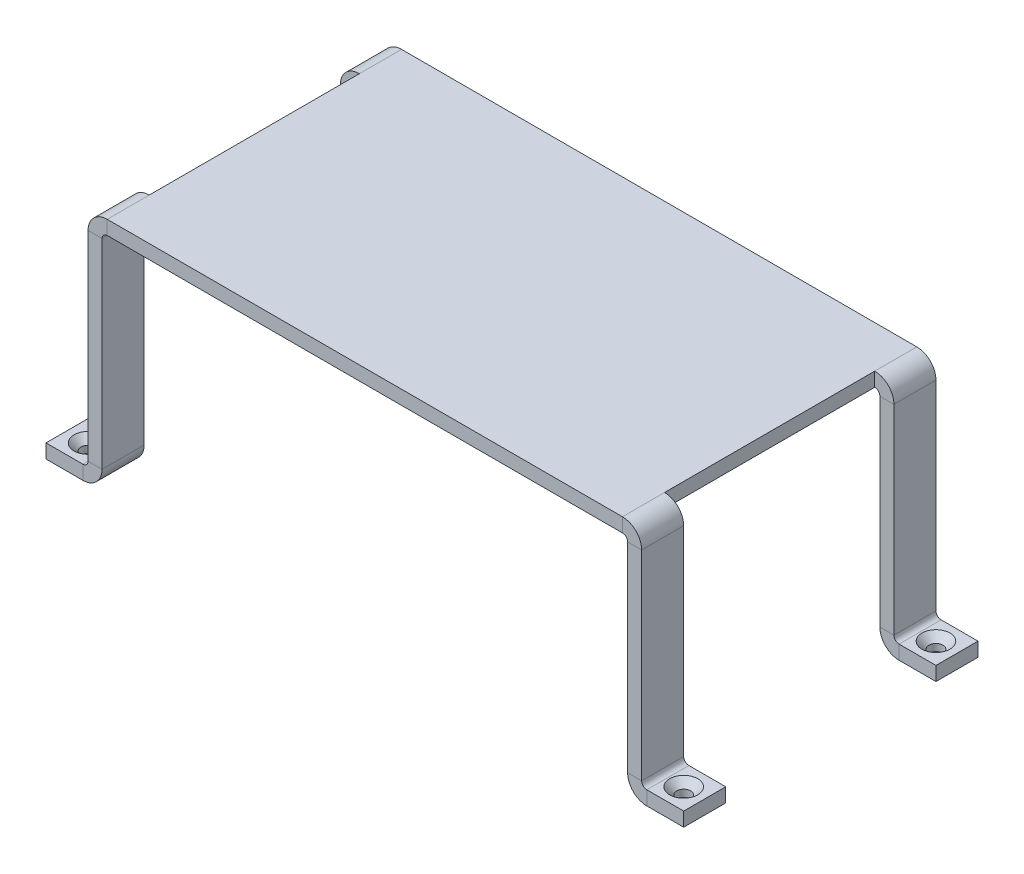
SolidWorks part; units mm, degrees
note: The reader was unsure of these and kept them because the rebuilt part matched: flange length of "边线-法兰1", "边线-法兰2", "边线-法兰3", "边线-法兰4".
ref_plane "前视基准面" through (0, 0, 0) normal (0, 0, 1) x (1, 0, 0)
ref_plane "上视基准面" through (0, 0, 0) normal (0, 1, 0) x (1, 0, 0)
ref_plane "右视基准面" through (0, 0, 0) normal (1, 0, 0) x (0, 0, -1)
sketch "草图2" plane through (0, 0, 0) normal (0, 1, 0) x (1, 0, 0)
  line L1 (-15.533, 15.3774) -> (59.467, 15.3774)
  line L2 (-15.533, 15.3774) -> (-15.533, -26.6226)
  line L3 (-15.533, -26.6226) -> (59.467, -26.6226)
  line L4 (59.467, 15.3774) -> (59.467, -26.6226)
base flange "基体-法兰1" sketch "草图2" thickness 2 reverse thickness direction no parameters "D1"=0.7366
edge flange "边线-法兰1" sketch "草图9" flange angle 90 flange length 30 flange position material outside bend radius 0.7366 thickness 2 relief rectangular parameters "D6"=10
sketch "草图9" plane through (-15.533, -2, 0) normal (1, 0, 0) x (0, 0, 1)
  line L2 (-15.3774, 0) -> (-15.3774, 30)
  line L3 (-15.3774, 30) -> (26.6226, 30)
  line L4 (26.6226, 30) -> (26.6226, 0)
  line L5 (26.6226, 0) -> (-15.3774, 0) construction
  line L6 (26.6226, 0) -> (-15.3774, 0)
bend "边线折弯1" bend radius 0.7366 bend angle 90 parameters "D5"=1
edge flange "边线-法兰2" sketch "草图12" flange angle 90 flange length 30 flange position material outside bend radius 0.7366 thickness 2 relief rectangular parameters "D6"=10
sketch "草图12" plane through (59.467, -2, 0) normal (-1, 0, 0) x (0, 0, -1)
  line L2 (-26.6226, 0) -> (-26.6226, 30)
  line L3 (-26.6226, 30) -> (15.3774, 30)
  line L4 (15.3774, 30) -> (15.3774, 0)
  line L5 (15.3774, 0) -> (-26.6226, 0) construction
  line L6 (15.3774, 0) -> (-26.6226, 0)
bend "边线折弯2" bend radius 0.7366 bend angle 90 parameters "D5"=2
edge flange "边线-法兰3" sketch "草图15" flange angle 90 flange length 6 flange position material outside bend radius 0.7366 thickness 2 relief rectangular parameters "D6"=10
sketch "草图15" plane through (-17.533, -32, 0) normal (0, 1, 0) x (0, 0, -1)
  line L2 (-26.6226, 0) -> (-26.6226, 6)
  line L3 (-26.6226, 6) -> (15.3774, 6)
  line L4 (15.3774, 6) -> (15.3774, 0)
  line L8 (15.3774, 0) -> (-26.6226, 0) construction
  line L9 (15.3774, 0) -> (-26.6226, 0)
bend "边线折弯3" bend radius 0.7366 bend angle 90 parameters "D5"=3
edge flange "边线-法兰4" sketch "草图18" flange angle 90 flange length 6 flange position material outside bend radius 0.7366 thickness 2 relief rectangular parameters "D6"=10
sketch "草图18" plane through (61.467, -32, 0) normal (0, 1, 0) x (0, 0, 1)
  line L2 (-15.3774, 0) -> (-15.3774, 6)
  line L3 (-15.3774, 6) -> (26.6226, 6)
  line L4 (26.6226, 6) -> (26.6226, 0)
  line L5 (26.6226, 0) -> (-15.3774, 0) construction
  line L6 (26.6226, 0) -> (-15.3774, 0)
bend "边线折弯4" bend radius 0.7366 bend angle 90 parameters "D5"=4
hole_wizard "M2*4" positions "草图25" profile "草图26" countersink size "M2" standard "GB" end condition through all
sketch "草图25" plane through (0, -32, 0) normal (0, 1, 0) x (1, 0, 0)
  line L0 (-23.533, -26.6226) -> (-18.2696, -26.6226) construction
  line L1 (-23.533, 15.3774) -> (-23.533, -26.6226) construction
  line L2 (-18.2696, 15.3774) -> (-23.533, 15.3774) construction
  line L3 (67.467, -26.6226) -> (67.467, 15.3774) construction
  line L4 (67.467, 15.3774) -> (62.2036, 15.3774) construction
  line L5 (62.2036, -26.6226) -> (67.467, -26.6226) construction
  point P0 (-20.533, 12.3774)
  point P2 (-20.533, -23.6226)
  point P4 (64.467, 12.3774)
  point P6 (64.467, -23.6226)
  point P14 (-20.9013, -26.6226)
  dimension "D1" = 3
  dimension "D2" = 3
  dimension "D3" = 3
  dimension "D4" = 3
  dimension "D5" = 3
  dimension "D6" = 3
  dimension "D7" = 3
  dimension "D8" = 3
sketch "草图26" plane through (-20.533, -32, -12.3774) normal (1, 0, 0) x (0, 0, 1)
  line L0 (0, 0) -> (0, 2)
  line L1 (0, 2) -> (1, 2)
  line L2 (1, 2) -> (1, 1)
  line L3 (1, 1) -> (2, 0)
  line L5 (2, 0) -> (0, 0)
  line L6 (-1, 1) -> (-2, 0) construction
  line L11 (0, -6.35) -> (0, 107.95) construction
  dimension "通孔孔直径" = 2
  dimension "通孔孔深度" = 2
  dimension "近端锥形沉头孔直径" = 4
  dimension "近端锥形沉头孔角度" = 90
sketch "草图27" plane through (0, 0, 0) normal (0, 1, 0) x (1, 0, 0)
  line L0 (-23.533, 15.3774) -> (-23.533, -26.6226) construction
  line L1 (-23.533, 9.3774) -> (-14.7964, 9.3774)
  line L2 (-23.533, 9.3774) -> (-23.533, -20.6226)
  line L3 (-23.533, -20.6226) -> (-14.7964, -20.6226)
  line L4 (-14.7964, 9.3774) -> (-14.7964, -20.6226)
  line L5 (58.7304, 9.3774) -> (67.467, 9.3774)
  line L6 (58.7304, 9.3774) -> (58.7304, -20.6226)
  line L7 (58.7304, -20.6226) -> (67.467, -20.6226)
  line L8 (67.467, 9.3774) -> (67.467, -20.6226)
  line L9 (-14.7964, 15.3774) -> (-14.7964, -26.6226) construction
  line L10 (67.467, -26.6226) -> (67.467, 15.3774) construction
  line L11 (58.7304, -26.6226) -> (58.7304, 15.3774) construction
  line L12 (58.7304, 15.3774) -> (-14.7964, 15.3774) construction
  line L13 (-14.7964, -26.6226) -> (58.7304, -26.6226) construction
  point P18 (-19.1647, -20.6226)
  dimension "D1" = 0
  dimension "D2" = 0
  dimension "D3" = 0
  dimension "D4" = 0
  dimension "D5" = 6
  dimension "D6" = 6
  dimension "D7" = 6
  dimension "D8" = 6
extrude "切除-拉伸" cut sketch "草图27" against normal blind 38 normal cut yes
sketch "折弯-线1" [suppressed] plane through (0, 0, 0) normal (0, 1, 0) x (1, 0, 0)
sketch "边界框1" [suppressed] plane through (0, 0, 0) normal (0, 1, 0) x (1, 0, 0)
sheet metal parameters "钣金2" thickness 2 parameters "D1"=0.7366
flat pattern "平板型式2" [suppressed]
sketch "折弯-线2" plane through (0, 0, 0) normal (0, 1, 0) x (1, 0, 0)
sketch3d "边界框2" [suppressed]
  line L0 (-57.6671, -26.0485, 0) -> (27.8506, -26.0485, 0) construction
  line L1 (-57.6671, 26.0485, 0) -> (27.8506, 26.0485, 0) construction
  line L2 (-57.6671, -26.0485, 0) -> (-57.6671, 26.0485, 0) construction
  line L3 (27.8506, -26.0485, 0) -> (27.8506, 26.0485, 0) construction
sheet metal parameters "钣金3" thickness 2 parameters "D1"=0.7366
flat pattern "平板型式2"
sketch "折弯-线2" plane through (0, 0, 0) normal (0, 1, 0) x (1, 0, 0)
  line L0 (-26.4779, 26.0485) -> (-26.4779, -26.0485) construction
  line L1 (-26.4779, 26.0485) -> (-26.4779, -26.0485) construction
sketch3d "边界框2" [suppressed]
  line L0 (57.6671, -26.0485, 0) -> (-45.1052, -26.0485, 0) construction
  line L1 (57.6671, 26.0485, 0) -> (-45.1052, 26.0485, 0) construction
  line L2 (57.6671, -26.0485, 0) -> (57.6671, 26.0485, 0) construction
  line L3 (-45.1052, -26.0485, 0) -> (-45.1052, 26.0485, 0) construction
bend of the flat pattern "展平-<边线折弯1>1"
sheet metal parameters "钣金4" thickness 2 parameters "D1"=0.7366
flat pattern "平板型式2"
sketch "折弯-线2" plane through (0, 0, 0) normal (0, 1, 0) x (1, 0, 0)
  line L0 (-26.4779, 26.0485) -> (-26.4779, -26.0485) construction
  line L1 (-26.4779, 26.0485) -> (-26.4779, -26.0485) construction
  line L2 (56.2944, -26.0485) -> (56.2944, 26.0485) construction
  line L3 (56.2944, -26.0485) -> (56.2944, 26.0485) construction
sketch3d "边界框2" [suppressed]
  line L0 (84.9217, -26.0485, 0) -> (-55.1052, -26.0485, 0) construction
  line L1 (84.9217, 26.0485, 0) -> (-55.1052, 26.0485, 0) construction
  line L2 (84.9217, -26.0485, 0) -> (84.9217, 26.0485, 0) construction
  line L3 (-55.1052, -26.0485, 0) -> (-55.1052, 26.0485, 0) construction
bend of the flat pattern "展平-<边线折弯1>1"
bend of the flat pattern "展平-<边线折弯2>1"
sheet metal parameters "钣金5" thickness 2 parameters "D1"=0.7366
flat pattern "平板型式2"
sketch "折弯-线2" plane through (0, 0, 0) normal (0, 1, 0) x (1, 0, 0)
  line L0 (-26.4779, 26.0485) -> (-26.4779, -26.0485) construction
  line L1 (-26.4779, 26.0485) -> (-26.4779, -26.0485) construction
  line L2 (56.2944, -26.0485) -> (56.2944, 26.0485) construction
  line L3 (56.2944, -26.0485) -> (56.2944, 26.0485) construction
  line L4 (-53.7326, 26.0485) -> (-53.7326, -26.0485) construction
  line L5 (-53.7326, 26.0485) -> (-53.7326, -26.0485) construction
sketch3d "边界框2" [suppressed]
  line L0 (84.9217, -26.0485, 0) -> (-59.3599, -26.0485, 0) construction
  line L1 (84.9217, 26.0485, 0) -> (-59.3599, 26.0485, 0) construction
  line L2 (84.9217, -26.0485, 0) -> (84.9217, 26.0485, 0) construction
  line L3 (-59.3599, -26.0485, 0) -> (-59.3599, 26.0485, 0) construction
bend of the flat pattern "展平-<边线折弯1>1"
bend of the flat pattern "展平-<边线折弯2>1"
bend of the flat pattern "展平-<边线折弯3>1"
sheet metal parameters "钣金6" thickness 2 parameters "D1"=0.7366
flat pattern "平板型式2"
sketch "折弯-线2" plane through (0, 0, 0) normal (0, 1, 0) x (1, 0, 0)
  line L0 (-26.4779, 26.0485) -> (-26.4779, -26.0485) construction
  line L1 (-26.4779, 26.0485) -> (-26.4779, -26.0485) construction
  line L2 (56.2944, -26.0485) -> (56.2944, 26.0485) construction
  line L3 (56.2944, -26.0485) -> (56.2944, 26.0485) construction
  line L4 (-53.7326, 26.0485) -> (-53.7326, -26.0485) construction
  line L5 (-53.7326, 26.0485) -> (-53.7326, -26.0485) construction
  line L6 (83.5491, -26.0485) -> (83.5491, 26.0485) construction
  line L7 (83.5491, -26.0485) -> (83.5491, 26.0485) construction
sketch3d "边界框2" [suppressed]
  line L0 (89.1764, -26.0485, 0) -> (-59.3599, -26.0485, 0) construction
  line L1 (89.1764, 26.0485, 0) -> (-59.3599, 26.0485, 0) construction
  line L2 (89.1764, -26.0485, 0) -> (89.1764, 26.0485, 0) construction
  line L3 (-59.3599, -26.0485, 0) -> (-59.3599, 26.0485, 0) construction
bend of the flat pattern "展平-<边线折弯1>1"
bend of the flat pattern "展平-<边线折弯2>1"
bend of the flat pattern "展平-<边线折弯3>1"
bend of the flat pattern "展平-<边线折弯4>1"
sheet metal parameters "钣金9" thickness 2 parameters "D1"=0.7366
flat pattern "平板型式2"
sketch "折弯-线2" plane through (0, 0, 0) normal (0, 1, 0) x (1, 0, 0)
  line L0 (-16.1604, 15.3774) -> (-16.1604, -26.6226) construction
  line L1 (-16.1604, 15.3774) -> (-16.1604, -26.6226) construction
  line L2 (60.0943, -26.6226) -> (60.0943, 15.3774) construction
  line L3 (60.0943, -26.6226) -> (60.0943, 15.3774) construction
  line L4 (-47.415, 15.3774) -> (-47.415, -26.6226) construction
  line L5 (-47.415, 15.3774) -> (-47.415, -26.6226) construction
  line L6 (91.3489, -26.6226) -> (91.3489, 15.3774) construction
  line L7 (91.3489, -26.6226) -> (91.3489, 15.3774) construction
sketch3d "边界框2" [suppressed]
  line L0 (97.9762, -26.6226, 0) -> (-54.0423, -26.6226, 0) construction
  line L1 (97.9762, 15.3774, 0) -> (-54.0423, 15.3774, 0) construction
  line L2 (97.9762, -26.6226, 0) -> (97.9762, 15.3774, 0) construction
  line L3 (-54.0423, -26.6226, 0) -> (-54.0423, 15.3774, 0) construction
bend of the flat pattern "展平-<边线折弯1>1"
bend of the flat pattern "展平-<边线折弯2>1"
bend of the flat pattern "展平-<边线折弯3>1"
bend of the flat pattern "展平-<边线折弯4>1"
sheet metal parameters "钣金18" thickness 2 parameters "D1"=0.7366
flat pattern "平板型式2"
sketch "折弯-线2" plane through (0, 0, 0) normal (0, 1, 0) x (1, 0, 0)
  line L0 (-16.1604, 15.3774) -> (-16.1604, 9.3774) construction
  line L1 (-16.1604, 15.3774) -> (-16.1604, 9.3774) construction
  line L2 (60.0943, 9.3774) -> (60.0943, 15.3774) construction
  line L3 (60.0943, 9.3774) -> (60.0943, 15.3774) construction
  line L4 (-47.415, 15.3774) -> (-47.415, 9.3774) construction
  line L5 (-47.415, 15.3774) -> (-47.415, 9.3774) construction
  line L6 (91.3489, 9.3774) -> (91.3489, 15.3774) construction
  line L7 (91.3489, 9.3774) -> (91.3489, 15.3774) construction
  line L8 (91.3489, -26.6226) -> (91.3489, -20.6226) construction
  line L9 (-47.415, -20.6226) -> (-47.415, -26.6226) construction
  line L10 (60.0943, -26.6226) -> (60.0943, -20.6226) construction
  line L11 (-16.1604, -20.6226) -> (-16.1604, -26.6226) construction
sketch3d "边界框2" [suppressed]
  line L0 (97.9762, -26.6226, 0) -> (-54.0423, -26.6226, 0) construction
  line L1 (97.9762, 15.3774, 0) -> (-54.0423, 15.3774, 0) construction
  line L2 (97.9762, -26.6226, 0) -> (97.9762, 15.3774, 0) construction
  line L3 (-54.0423, -26.6226, 0) -> (-54.0423, 15.3774, 0) construction
bend of the flat pattern "展平-<边线折弯1>1"
bend of the flat pattern "展平-<边线折弯2>1"
bend of the flat pattern "展平-<边线折弯3>1"
bend of the flat pattern "展平-<边线折弯4>1"
